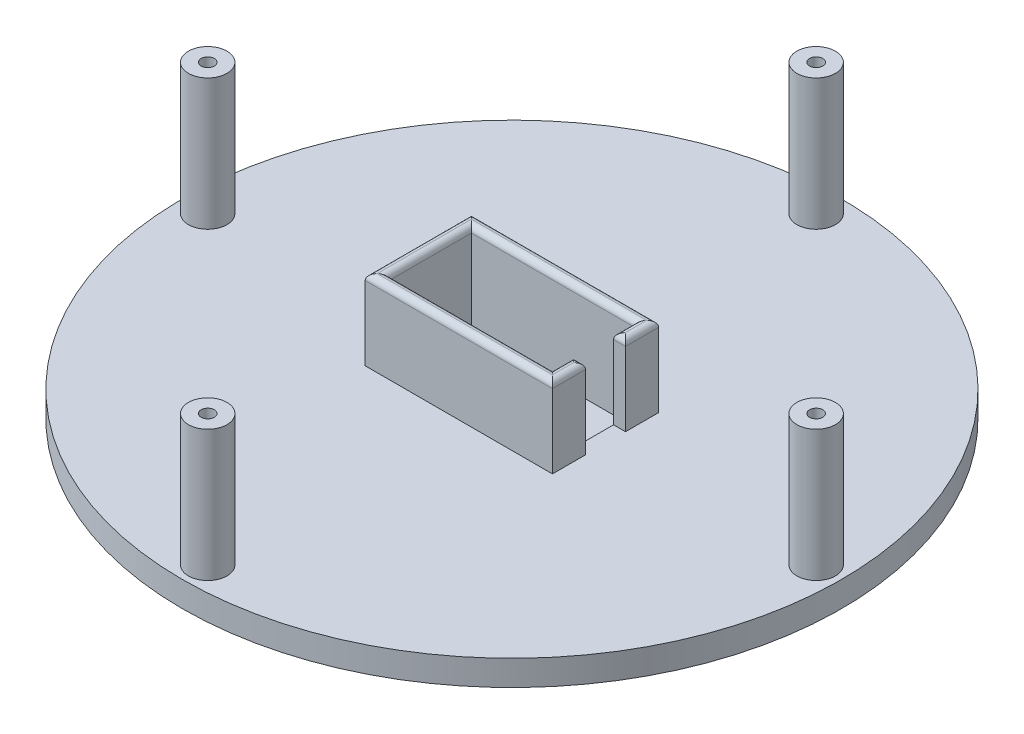
SolidWorks part; units mm, degrees
ref_plane "Front Plane" through (0, 0, 0) normal (0, 0, 1) x (1, 0, 0)
ref_plane "Top Plane" through (0, 0, 0) normal (0, 1, 0) x (1, 0, 0)
ref_plane "Right Plane" through (0, 0, 0) normal (1, 0, 0) x (0, 0, -1)
sketch "Sketch1" plane through (0, 0, 0) normal (0, 1, 0) x (1, 0, 0)
  circle A0 centre (0, 0) radius 82.55
  dimension "D1" = 165.1
extrude "Boss-Extrude2" add sketch "Sketch1" along normal blind 6.35 contours A0
sketch "Sketch2" plane through (0, 6.35, 0) normal (0, 1, 0) x (1, 0, 0)
  line L1 (-20.45, 10.3) -> (20.45, 10.3)
  line L2 (-20.45, 10.3) -> (-20.45, -10.3)
  line L3 (-20.45, -10.3) -> (20.45, -10.3)
  line L4 (20.45, 10.3) -> (20.45, -10.3)
  line L5 (-20.45, 10.3) -> (20.45, -10.3) construction
  line L6 (-20.45, -10.3) -> (20.45, 10.3) construction
  point P0 (0, 0)
  dimension "D1" = 40.9
  dimension "D2" = 20.6
extrude "Cut-Extrude1" cut sketch "Sketch2" against normal blind 3.175
sketch "Sketch3" plane through (0, 6.35, 0) normal (0, 1, 0) x (1, 0, 0)
  line L0 (-82.55, 0) -> (82.55, 0) construction
  line L1 (0, 82.55) -> (0, -82.55) construction
  circle A0 centre (0, 0) radius 82.55 construction
  circle A1 centre (0, 76.2) radius 1.65
  dimension "D1" = 3.3
  dimension "D2" = 76.2
extrude "Cut-Extrude2" cut sketch "Sketch3" against normal up to next
pattern_circular "CirPattern1" count 4 over 360 about axis through (0, 6.35, 0) along (0, 1, 0) of "Cut-Extrude2"
sketch "Sketch5" plane through (0, 6.35, 0) normal (0, 1, 0) x (1, 0, 0)
  circle A0 centre (0, 76.2) radius 1.65
  circle A1 centre (0, 76.2) radius 4.825
  dimension "D1" = 3.3
  dimension "D2" = 3.175
extrude "Boss-Extrude3" add sketch "Sketch5" along normal blind 32.825
pattern_circular "CirPattern3" count 4 over 360 about axis through (0, 6.35, 0) along (0, 1, 0) of "Boss-Extrude3"
sketch "Sketch4" plane through (0, 0, 0) normal (0, -1, 0) x (1, 0, 0)
  circle A0 centre (-76.2, 0) radius 2.9
  dimension "D1" = 5.8
extrude "Cut-Extrude3" cut sketch "Sketch4" against normal blind 20 contours A0
pattern_circular "CirPattern4" count 4 over 360 about axis through (0, 0, 0) along (0, 1, 0) of "Cut-Extrude3"
sketch "Sketch6" plane through (0, 6.35, 0) normal (0, 1, 0) x (1, 0, 0)
  line L0 (-20.45, 10.3) -> (20.45, 10.3)
  line L1 (20.45, 10.3) -> (20.45, 5)
  line L2 (20.45, 5) -> (23.45, 5)
  line L3 (23.45, 5) -> (23.45, 13.3)
  line L4 (23.45, 13.3) -> (-23.45, 13.3)
  line L5 (-23.45, 13.3) -> (-23.45, -13.3)
  line L6 (-23.45, -13.3) -> (23.45, -13.3)
  line L9 (-20.45, -10.3) -> (-20.45, 10.3)
  line L10 (-20.45, 10.3) -> (-20.45, -10.3) construction
  line L13 (-20.45, -10.3) -> (20.45, -10.3)
  line L14 (20.45, -10.3) -> (20.45, -5)
  line L15 (20.45, -5) -> (23.45, -5)
  line L16 (23.45, -5) -> (23.45, -13.3)
  line L17 (-20.45, -10.3) -> (20.45, -10.3) construction
  line L18 (20.45, 10.3) -> (-20.45, 10.3) construction
  line L19 (20.45, -10.3) -> (20.45, 10.3) construction
  line L20 (0, 10.3) -> (0, 5) construction
  line L21 (0, 5) -> (20.45, 5) construction
  line L22 (0, -10.3) -> (0, -5) construction
  line L23 (0, -5) -> (20.45, -5) construction
  dimension "D1" = 3
  dimension "D2" = 3
  dimension "D3" = 3
  dimension "D4" = 3
  dimension "D5" = 10
extrude "Boss-Extrude5" add sketch "Sketch6" along normal blind 20
fillet "Fillet1" radius 1.5 12 edges at (0, 26.35, 10.3) (20.45, 26.35, 7.65) (21.95, 26.35, 5) (23.45, 26.35, 9.15) (0, 26.35, 13.3) (-23.45, 26.35, 0) (0, 26.35, -13.3) (23.45, 26.35, -9.15) (21.95, 26.35, -5) (20.45, 26.35, -7.65) (0, 26.35, -10.3) (-20.45, 26.35, 0)
